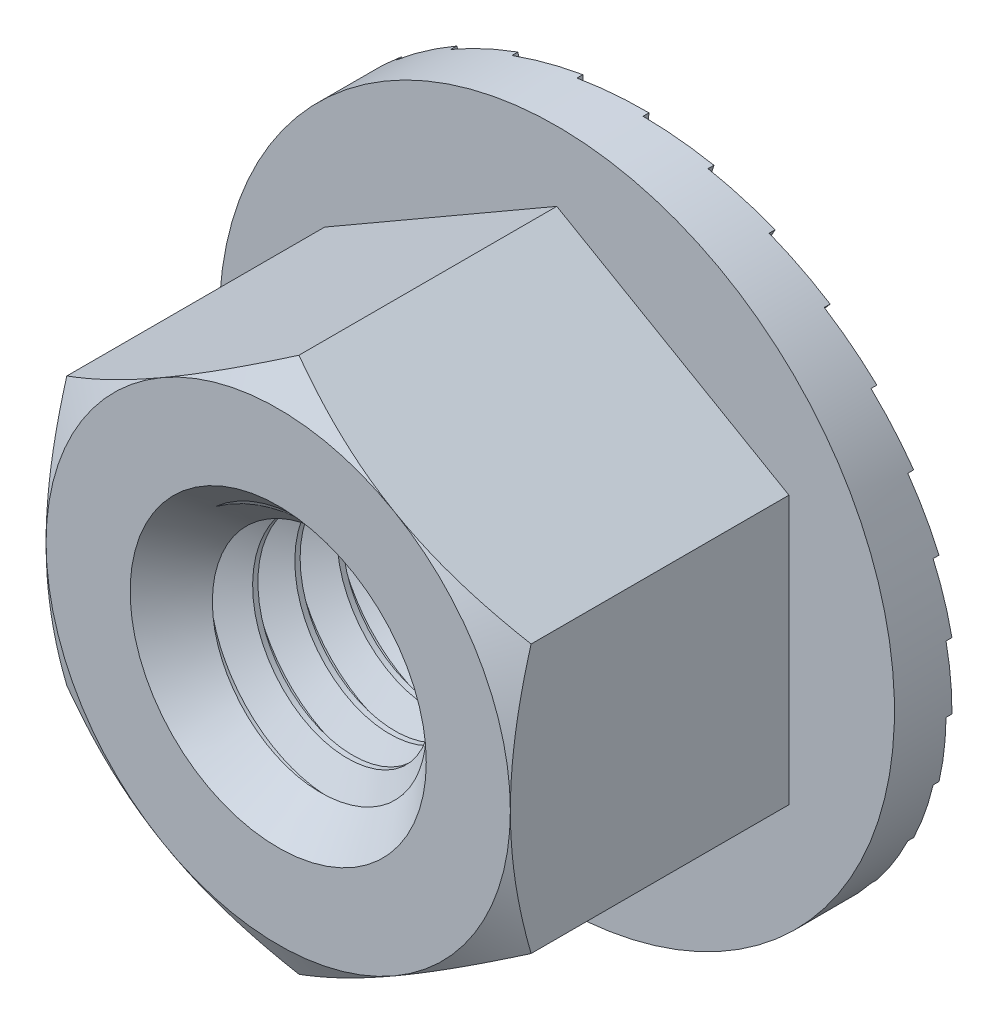
SolidWorks part; units mm, degrees
ref_plane "Front Plane" through (0, 0, 0) normal (0, 0, 1) x (1, 0, 0)
ref_plane "Top Plane" through (0, 0, 0) normal (0, 1, 0) x (1, 0, 0)
ref_plane "Right Plane" through (0, 0, 0) normal (1, 0, 0) x (0, 0, -1)
sketch "Sketch1" plane through (0, 0, 0) normal (0, 0, 1) x (1, 0, 0)
  line L1 (0, 3.1754) -> (-2.75, 1.5877)
  line L2 (-2.75, 1.5877) -> (-2.75, -1.5877)
  line L3 (-2.75, -1.5877) -> (0, -3.1754)
  line L4 (0, -3.1754) -> (2.75, -1.5877)
  line L5 (2.75, -1.5877) -> (2.75, 1.5877)
  line L6 (2.75, 1.5877) -> (0, 3.1754)
  circle A0 centre (0, 0) radius 2.75 construction
  dimension "Hex" = 5.5
extrude "Extrude1" add sketch "Sketch1" against normal blind 4
sketch "Sketch13" plane through (0, 0, -4) normal (0, 0, -1) x (-1, 0, 0)
  circle A0 centre (0, 0) radius 4
  dimension "Flange od" = 8
extrude "Extrude3" add sketch "Sketch13" against normal blind 0.7
sketch "Sketch2" plane through (0, 0, 0) normal (0, 0, 1) x (1, 0, 0)
  circle A0 centre (0, 0) radius 2.75 construction
  circle A1 centre (0, 0) radius 2.75
extrude "Cut-Extrude1" cut sketch "Sketch2" against normal through all draft 60 flip side to cut
sketch "Sketch4" plane through (0, 0, 0) normal (0, 0, 1) x (1, 0, 0)
  circle A0 centre (0, 0) radius 1.5
  dimension "Thread Dia" = 3
extrude "Cut-Extrude3" cut sketch "Sketch4" against normal through all
sketch "Sketch7" plane through (0, 0, 0) normal (0, 0, 1) x (1, 0, 0)
  circle A4 centre (0, 0) radius 1.754
  circle A5 centre (0, 0) radius 1.754
  dimension "D1" = 0.254
sketch "Sketch8" plane through (0, 0, -4) normal (0, 0, -1) x (-1, 0, 0)
  circle A1 centre (0, 0) radius 1.754
  circle A2 centre (0, 0) radius 1.754 construction
sketch "Sketch5" plane through (0, 0, 0) normal (0, 0, 1) x (1, 0, 0)
  circle A0 centre (0, 0) radius 1.5 construction
  circle A1 centre (0, 0) radius 1.5
curve "Helix/Spiral1" pitch 0.5 height 4.5 radius 1.5 centre (0, 0, 0) axis (0, 0, -1) start towards (0, 1, 0) parameters "pitch"=0.5
sketch "Sketch9" plane through (0, 0, 0) normal (1, 0, 0) x (0, 0, -1)
  line L0 (-0.25, 1.5) -> (-0.1875, 1.5)
  line L1 (-0.1875, 1.5) -> (0, 1.1752)
  line L2 (-0.25, 1.5) -> (-0.4375, 1.1752)
  line L3 (-0.4375, 1.1752) -> (0, 1.1752)
  line L4 (-0.2188, 1.5) -> (-0.2188, 1.1752) construction
  line L5 (-0.3438, 1.3376) -> (-0.0938, 1.3376) construction
  line L7 (0, 1.1752) -> (0, 1.5) construction
  line L8 (0, 1.5) -> (0, -1.5) construction
  dimension "D1" = 0.0625
  dimension "D2" = 0.25
  dimension "D3" = 60
sketch "Sketch12" plane through (0, 0, 0) normal (0, 0, 1) x (1, 0, 0)
  circle A0 centre (0, 0) radius 1.1752
  circle A1 centre (0, 0) radius 1.5 construction
  circle A2 centre (0, 0) radius 1.5
extrude "Extrude2" add sketch "Sketch12" against normal up to surface (4 mm away) up to face at (1.5, 0, -4)
sweep "Cut-Sweep1" cut profiles "Sketch9" path "Helix/Spiral1" align with end faces yes
extrude "Cut-Extrude6" cut sketch "Sketch7" against normal through all draft 45
extrude "Cut-Extrude7" cut sketch "Sketch8" against normal through all draft 45
sketch "Sketch14" plane through (0, 0, -4) normal (0, 0, -1) x (-1, 0, 0)
  circle A4 centre (0, 0) radius 2.254
  circle A5 centre (0, 0) radius 2.254
  dimension "D1" = 0.5
extrude "Cut-Extrude8" cut sketch "Sketch14" against normal blind 0.07 flip side to cut
sketch "Sketch15" plane through (0, 0, -3.93) normal (0, 0, -1) x (-1, 0, 0)
  line L0 (-0.2209, 2.2431) -> (-0.3921, 3.9807)
  line L1 (0.2209, 2.2431) -> (0.3921, 3.9807)
  line L2 (0, 0) -> (0.2209, 2.2431) construction
  line L3 (0, 0) -> (-0.2209, 2.2431) construction
  circle A0 centre (0, 0) radius 4 construction
  circle A1 centre (0, 0) radius 2.254 construction
  arc A2 (0.3921, 3.9807) -> (-0.3921, 3.9807) centre (0, 0) ccw
  arc A3 (0.2209, 2.2431) -> (-0.2209, 2.2431) centre (0, 0) ccw
  dimension "D1" = 11.25
extrude "Extrude4" add sketch "Sketch15" along normal up to surface (0.07 mm away) separate body up to face at (-1.754, 0, -4)
sketch "Sketch16" plane through (0, 0, 0) normal (0, 1, 0) x (1, 0, 0)
  line L0 (-0.3921, 3.93) -> (0.3921, 4)
  line L4 (-0.3921, 3.93) -> (0.3921, 3.93)
  line L5 (0.3921, 3.93) -> (0.3921, 4)
  line L6 (0.3921, 4) -> (-0.3921, 4)
  line L7 (-0.3921, 4) -> (-0.3921, 3.93)
  line L8 (-0.3921, 3.93) -> (0.3921, 3.93) construction
  line L9 (0.3921, 3.93) -> (0.3921, 4) construction
  line L10 (0.3921, 4) -> (-0.3921, 4)
  line L11 (-0.3921, 4) -> (-0.3921, 3.93)
  dimension "D1" = 0
extrude "Cut-Extrude9" cut sketch "Sketch16" along normal through all
pattern_circular "CirPattern1" count 32 over 360 about axis through (0, 0, -5.9239) along (0, 0, 1) of bodies 119
combine bodies "Combine1" operation type add bodies to combine 117 119 120 121 122 123 124 125 126 127 128 129 130 131 132 133 134 135 136 137 139 140 141 142 143 144 145 146 147 148 149 150 151
sketch "Sketch17" plane through (0, 0, 0) normal (1, 0, 0) x (0, 0, -1)
  line L0 (4, 4) -> (4, -4) construction
  line L1 (3.3, 4) -> (3.3, -4) construction
  dimension "D1" = 0.7
sketch "Sketch18" plane through (0, 0, -3.3) normal (0, 0, 1) x (1, 0, 0)
  circle A0 centre (0, 0) radius 4
  circle A1 centre (0, 0) radius 4 construction
equation "\"D2@Sketch9\" = \"pitch@Helix/Spiral1\"*.5"
equation "\"D3@Helix/Spiral1\" = \"pitch@Helix/Spiral1\"+\"Height@Extrude1\""
equation "\"D1@Sketch9\" = \"pitch@Helix/Spiral1\"*.125"
equation "\"D1@Cut-Extrude8\" = \"flange thickness@Extrude3\"*.1"
equation "\"D1@Sketch17\" = \"flange thickness@Extrude3\""
